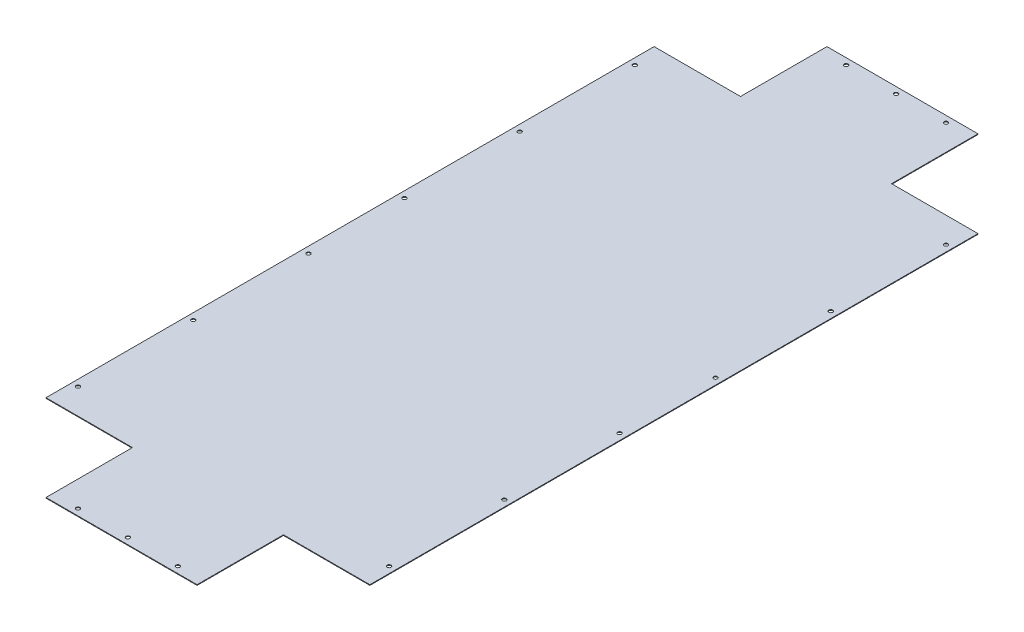
SolidWorks part; units mm, degrees
ref_plane "Front Plane" through (0, 0, 0) normal (0, 0, 1) x (1, 0, 0)
ref_plane "Top Plane" through (0, 0, 0) normal (0, 1, 0) x (1, 0, 0)
ref_plane "Right Plane" through (0, 0, 0) normal (1, 0, 0) x (0, 0, -1)
sketch "Sketch1" plane through (0, 0, 0) normal (0, 1, 0) x (1, 0, 0)
  line L0 (0, 610) -> (253, 610) construction
  line L1 (135, 0) -> (371, 0)
  line L2 (0, 135) -> (0, 1085)
  line L3 (135, 1220) -> (371, 1220)
  line L4 (506, 135) -> (506, 1085)
  line L7 (0, 1085) -> (135, 1085)
  line L8 (135, 1220) -> (135, 1085)
  line L9 (253, 610) -> (253, 1220) construction
  line L10 (506, 1085) -> (371, 1085)
  line L11 (371, 1220) -> (371, 1085)
  line L12 (0, 135) -> (135, 135)
  line L13 (135, 0) -> (135, 135)
  line L14 (371, 0) -> (371, 135)
  line L15 (506, 135) -> (371, 135)
  dimension "D1" = 506
  dimension "D2" = 1220
  dimension "D3" = 135
  dimension "D4" = 135
base flange "Base-Flange1" sketch "Sketch1" thickness 1 reverse thickness direction no parameters "D1"=1
sketch "Sketch6" plane through (0, 0, 0) normal (0, 1, 0) x (1, 0, 0)
  line L0 (506, 135) -> (506, 1085) construction
  line L1 (506, 1085) -> (371, 1085) construction
  line L2 (371, 1085) -> (371, 1220) construction
  line L3 (371, 1220) -> (135, 1220) construction
  line L4 (253, 1220) -> (253, 610) construction
  line L5 (253, 610) -> (506, 610) construction
  circle A0 centre (496, 1045) radius 3
  circle A1 centre (496, 865) radius 3
  circle A2 centre (496, 685) radius 3
  circle A3 centre (331, 1210) radius 3
  circle A4 centre (175, 1210) radius 3
  circle A5 centre (10, 685) radius 3
  circle A6 centre (10, 865) radius 3
  circle A7 centre (10, 1045) radius 3
  circle A8 centre (253, 1209.9973) radius 3
  circle A9 centre (253, 10.0027) radius 3
  circle A10 centre (10, 175) radius 3
  circle A11 centre (10, 355) radius 3
  circle A12 centre (10, 535) radius 3
  circle A13 centre (175, 10) radius 3
  circle A14 centre (331, 10) radius 3
  circle A15 centre (496, 535) radius 3
  circle A16 centre (496, 355) radius 3
  circle A17 centre (496, 175) radius 3
  point P47 (0, 0)
  dimension "D1" = 6
  dimension "D3" = 40
  dimension "D5" = 40
  dimension "D6" = 10
  dimension "D2" = 10
  dimension "D4" = 3
extrude "Cut-Extrude1" cut sketch "Sketch6" against normal blind 10 normal cut yes
sketch "Bend-Lines1" [suppressed] plane through (0, 0, 0) normal (0, 1, 0) x (1, 0, 0)
sketch "Bounding-Box1" [suppressed] plane through (0, 0, 0) normal (0, 1, 0) x (1, 0, 0)
sheet metal parameters "Sheet-Metal1" thickness 1 parameters "D1"=1
flat pattern "Flat-Pattern1" [suppressed]
sketch "Bend-Lines2" plane through (0, 0, 0) normal (0, 1, 0) x (1, 0, 0)
sketch3d "Bounding-Box2" [suppressed]
  line L0 (0, 1220, 0) -> (0, 0, 0) construction
  line L1 (-506.5, 1220, 0) -> (-506.5, 0, 0) construction
  line L2 (0, 1220, 0) -> (-506.5, 1220, 0) construction
  line L3 (0, 0, 0) -> (-506.5, 0, 0) construction
sheet metal parameters "Sheet-Metal2" thickness 1 parameters "D1"=1
flat pattern "Flat-Pattern1"
sketch "Bend-Lines2" plane through (0, 0, 0) normal (0, 1, 0) x (1, 0, 0)
sketch3d "Bounding-Box2" [suppressed]
  line L0 (0, 1220, 0) -> (0, 0, 0) construction
  line L1 (506, 1220, 0) -> (506, 0, 0) construction
  line L2 (0, 1220, 0) -> (506, 1220, 0) construction
  line L3 (0, 0, 0) -> (506, 0, 0) construction
